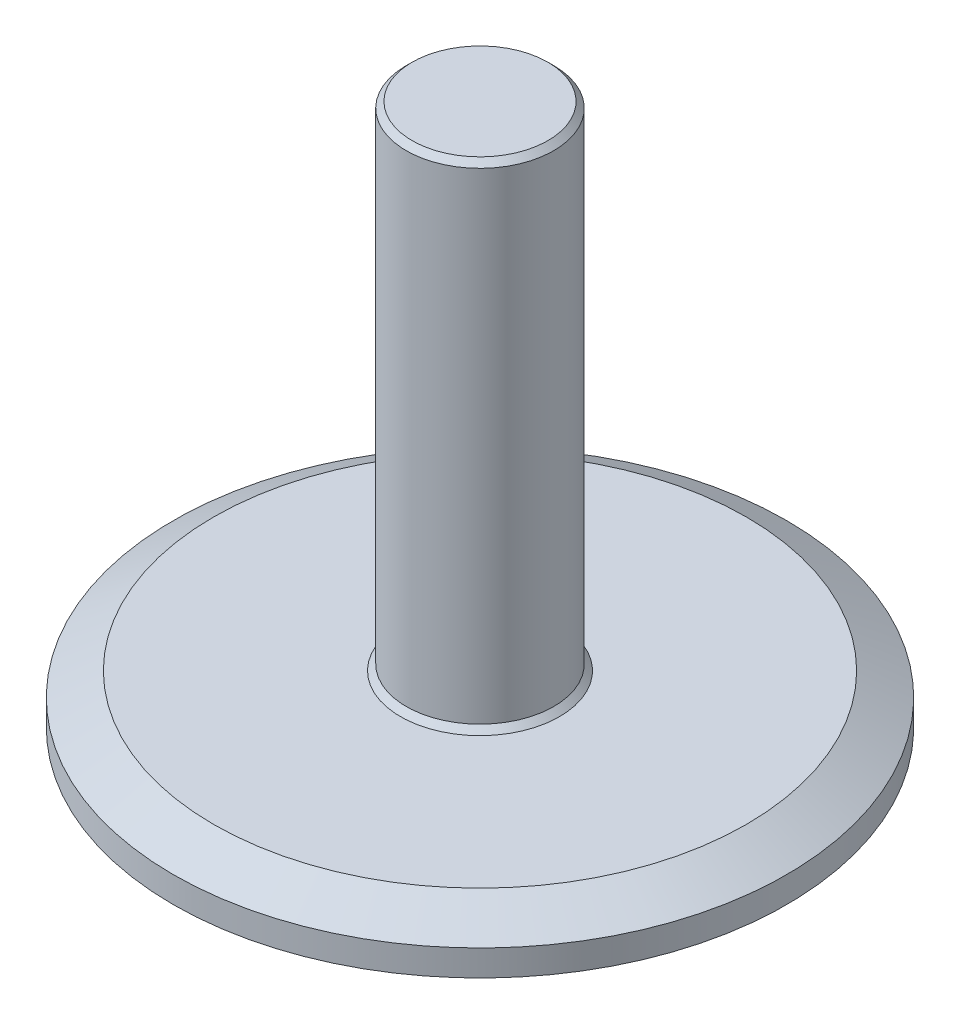
SolidWorks part; units mm, degrees
material "AISI 1020"
ref_plane "Plan de face" through (0, 0, 0) normal (0, 0, 1) x (1, 0, 0)
ref_plane "Plan de dessus" through (0, 0, 0) normal (0, 1, 0) x (1, 0, 0)
ref_plane "Plan de droite" through (0, 0, 0) normal (1, 0, 0) x (0, 0, -1)
sketch "Sketch1" plane through (0, 0, 0) normal (0, 0, 1) x (1, 0, 0)
  line L0 (0, 0) -> (0, 70.85)
  line L1 (0, 70.85) -> (-9.5, 70.85)
  line L2 (-9.5, 70.85) -> (-9.5, 7.35)
  line L3 (-9.5, 7.35) -> (-39.5, 7.35)
  line L4 (-39.5, 7.35) -> (-39.5, 1)
  line L5 (-39.5, 1) -> (-32, 1)
  line L6 (-32, 1) -> (-32, 0)
  line L7 (-32, 0) -> (0, 0)
  dimension "D1" = 32
  dimension "D2" = 30
  dimension "D3" = 9.5
  dimension "D4" = 63.5
  dimension "D5" = 6.35
  dimension "D6" = 1
revolve "Revolve1" add sketch "Sketch1" angle 360 about L0
chamfer "Chamfer1" distance 0.75 angle 45 2 edges at (0, 7.35, -9.5) (0, 70.85, -9.5)
chamfer "Chamfer2" distance 3 angle 60 1 edges at (0, 7.35, -39.5) first distance on face at (0, 1, -39.5)
hole_wizard "1/4-28 Tapped Hole2" positions "Sketch4" profile "Sketch5" tap size "1/4-28" standard "ANSI Inch"
sketch "Sketch4" plane through (0, 0, 0) normal (0, -1, 0) x (-1, 0, 0)
  point P0 (86.4837, -12.8235)
  point P2 (0, 0)
sketch "Sketch5" plane through (-86.4837, 0, 12.8235) normal (1, 0, 0) x (0, 0, -1)
  line L0 (0, 0) -> (0, 20.6254)
  line L1 (0, 20.6254) -> (2.7051, 19)
  line L2 (2.7051, 19) -> (2.7051, 0)
  line L5 (2.7051, 0) -> (0, 0)
  line L10 (0, 20.6254) -> (-2.7051, 19) construction
  line L11 (0, -6.35) -> (0, 107.95) construction
  dimension "Tap Drill Dia." = 5.4102
  dimension "Tap Drill Depth" = 19
  dimension "Drill Angle" = 118
cosmetic thread "Hole Thread1"
ref_axis "Axis1" through (0, 70.1, 0) along (0, -1, 0)
